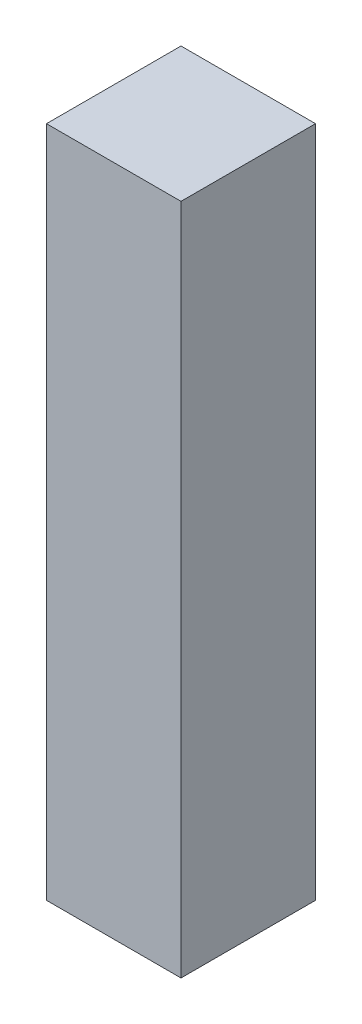
SolidWorks part; units mm, degrees
ref_plane "Front Plane" through (0, 0, 0) normal (0, 0, 1) x (1, 0, 0)
ref_plane "Top Plane" through (0, 0, 0) normal (0, 1, 0) x (1, 0, 0)
ref_plane "Right Plane" through (0, 0, 0) normal (1, 0, 0) x (0, 0, -1)
sketch "Sketch1" plane through (0, 0, 0) normal (0, 1, 0) x (1, 0, 0)
  line L1 (0, 0) -> (20, 0)
  line L2 (0, 0) -> (0, 20)
  line L3 (0, 20) -> (20, 20)
  line L4 (20, 0) -> (20, 20)
  dimension "D1" = 20
extrude "Boss-Extrude1" add sketch "Sketch1" along normal blind 100
